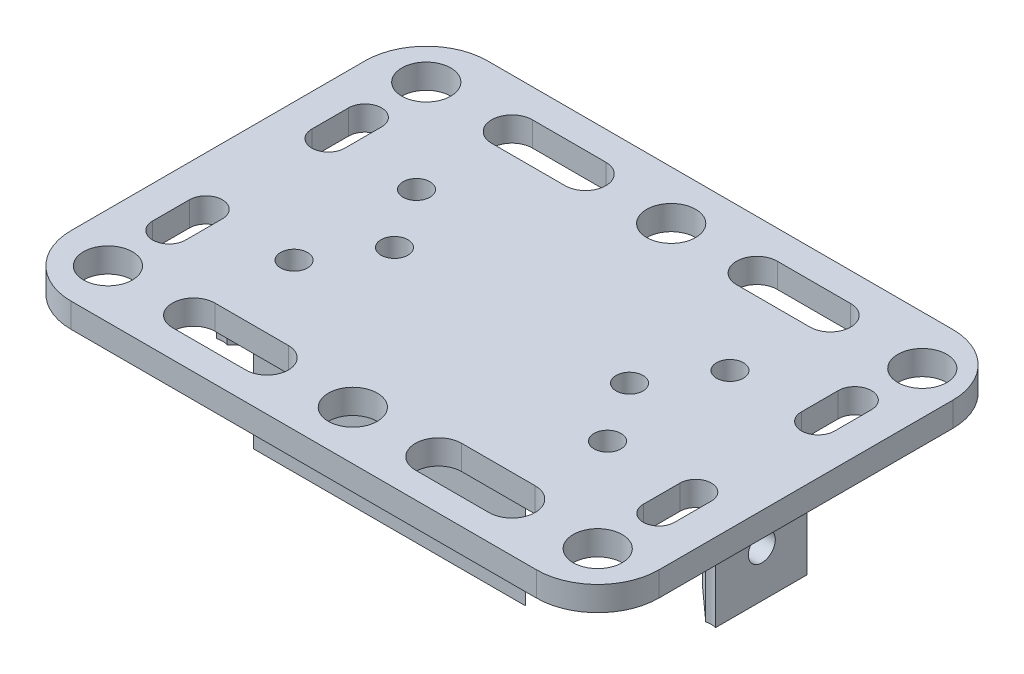
SolidWorks part; units mm, degrees
ref_plane "Front Plane" through (0, 0, 0) normal (0, 0, 1) x (1, 0, 0)
ref_plane "Top Plane" through (0, 0, 0) normal (0, 1, 0) x (1, 0, 0)
ref_plane "Right Plane" through (0, 0, 0) normal (1, 0, 0) x (0, 0, -1)
sketch "Sketch2" plane through (0, 0, 0) normal (0, 1, 0) x (1, 0, 0)
  line L0 (0, -55) -> (0, 55) construction
  line L1 (0, -42.5) -> (60, -42.5)
  line L2 (0, -42.5) -> (0, 42.5)
  line L3 (0, 42.5) -> (60, 42.5)
  line L4 (60, -42.5) -> (60, 42.5)
  line L5 (-55, 0) -> (55, 0) construction
  dimension "D1" = 60
  dimension "D2" = 85
  dimension "D3" = 42.5
extrude "Boss-Extrude1" add sketch "Sketch2" along normal blind 5
sketch "Sketch3" plane through (0, 0, 0) normal (0, -1, 0) x (1, 0, 0)
  line L0 (0, 25) -> (0, -25)
  line L1 (0, -2.75) -> (0, 2.75) construction
  line L2 (0, 25) -> (27.7753, 25)
  line L3 (27.7753, -25) -> (0.01, 0)
  line L4 (0.01, 0) -> (27.7753, 25)
  line L5 (2.75, 0) -> (-2.75, 0) construction
  line L6 (0, -25) -> (27.7753, -25)
  line L7 (0.01, 0) -> (38.51, 0) construction
  line L8 (38.51, 0) -> (51.01, 11.2551)
  line L10 (51.01, -11.2551) -> (38.51, 0)
  line L11 (51.01, 11.2551) -> (51.01, -11.2551)
  dimension "D1" = 42
  dimension "D2" = 42
  dimension "D3" = 0.01
  dimension "D4" = 38.5
  dimension "D5" = 12.5
  dimension "D6" = 25
  dimension "D7" = 42
  dimension "D8" = 25
  dimension "D9" = 42
extrude "Boss-Extrude2" add sketch "Sketch3" along normal blind 20
extrude "Boss-Extrude3" add sketch "Sketch3<2>" along normal blind 20
sketch "Sketch3<2>" plane through (0, 0, 0) normal (0, -1, 0) x (1, 0, 0) same geometry as "Sketch3"
fillet "Fillet1" radius 10 1 edges at (0.01, -10, 0)
fillet "Fillet2" radius 5 1 edges at (38.51, -10, 0)
fillet "Fillet3" radius 12.5 2 edges at (60, 2.5, 42.5) (60, 2.5, -42.5)
mirror "Mirror1" about plane through (0, 0, 0) normal (1, 0, 0) of "Fillet3", "Fillet2", "Fillet1", "Boss-Extrude3", "Boss-Extrude2", "Boss-Extrude1"
sketch "Sketch4" plane through (0, 5, 0) normal (0, 1, 0) x (1, 0, 0)
  line L1 (0, -2.75) -> (0, 2.75) construction
  line L4 (-47.5, -42.5) -> (47.5, -42.5) construction
  line L5 (47.5, 42.5) -> (-47.5, 42.5) construction
  line L6 (-32.5, 32.5) -> (-17.5, 32.5) construction
  line L7 (-32.5, 36.6576) -> (-17.5, 36.6576)
  line L8 (-32.5, 28.3424) -> (-17.5, 28.3424)
  line L9 (17.5, 32.5) -> (32.5, 32.5) construction
  line L10 (17.5, 36.6576) -> (32.5, 36.6576)
  line L11 (17.5, 28.3424) -> (32.5, 28.3424)
  line L12 (17.5, -32.5) -> (32.5, -32.5) construction
  line L13 (17.5, -27.7668) -> (32.5, -27.7668)
  line L14 (17.5, -37.2332) -> (32.5, -37.2332)
  line L15 (-32.5, -32.5) -> (-17.5, -32.5) construction
  line L16 (-32.5, -28.156) -> (-17.5, -28.156)
  line L17 (-32.5, -36.844) -> (-17.5, -36.844)
  line L18 (50, -20) -> (50, -12.5) construction
  line L19 (46.8051, -20) -> (46.8051, -12.5)
  line L20 (53.1949, -20) -> (53.1949, -12.5)
  line L21 (50, 20) -> (50, 12.5) construction
  line L22 (53.3895, 20) -> (53.3895, 12.5)
  line L23 (46.6105, 20) -> (46.6105, 12.5)
  line L24 (-50, 20) -> (-50, 12.5) construction
  line L25 (-46.6279, 20) -> (-46.6279, 12.5)
  line L26 (-53.3721, 20) -> (-53.3721, 12.5)
  line L27 (-50, -12.5) -> (-50, -20) construction
  line L28 (-46.6279, -12.5) -> (-46.6279, -20)
  line L29 (-53.3721, -12.5) -> (-53.3721, -20)
  circle A0 centre (-50, 32.5) radius 5
  circle A1 centre (0, 32.5) radius 5
  circle A2 centre (51.2765, 32.5) radius 5
  circle A3 centre (50, -32.5) radius 5
  circle A4 centre (0, -32.5) radius 5
  circle A5 centre (-50, -32.5) radius 5
  arc A8 (-32.5, 36.6576) -> (-32.5, 28.3424) centre (-32.5, 32.5) ccw
  arc A9 (-17.5, 28.3424) -> (-17.5, 36.6576) centre (-17.5, 32.5) ccw
  arc A10 (17.5, 36.6576) -> (17.5, 28.3424) centre (17.5, 32.5) ccw
  arc A11 (32.5, 28.3424) -> (32.5, 36.6576) centre (32.5, 32.5) ccw
  arc A12 (17.5, -27.7668) -> (17.5, -37.2332) centre (17.5, -32.5) ccw
  arc A13 (32.5, -37.2332) -> (32.5, -27.7668) centre (32.5, -32.5) ccw
  arc A14 (-32.5, -28.156) -> (-32.5, -36.844) centre (-32.5, -32.5) ccw
  arc A15 (-17.5, -36.844) -> (-17.5, -28.156) centre (-17.5, -32.5) ccw
  arc A16 (46.8051, -20) -> (53.1949, -20) centre (50, -20) ccw
  arc A17 (53.1949, -12.5) -> (46.8051, -12.5) centre (50, -12.5) ccw
  arc A18 (53.3895, 20) -> (46.6105, 20) centre (50, 20) ccw
  arc A19 (46.6105, 12.5) -> (53.3895, 12.5) centre (50, 12.5) ccw
  arc A20 (-46.6279, 20) -> (-53.3721, 20) centre (-50, 20) ccw
  arc A21 (-53.3721, 12.5) -> (-46.6279, 12.5) centre (-50, 12.5) ccw
  arc A22 (-46.6279, -12.5) -> (-53.3721, -12.5) centre (-50, -12.5) ccw
  arc A23 (-53.3721, -20) -> (-46.6279, -20) centre (-50, -20) ccw
  point P30 (-25, 32.5)
  point P35 (25, 32.5)
  point P42 (25, -32.5)
  point P49 (-25, -32.5)
  point P56 (50, -16.25)
  point P63 (50, 16.25)
  point P70 (-50, 16.25)
  point P77 (-50, -16.25)
  dimension "D2" = 10
  dimension "D3" = 10
  dimension "D4" = 10
  dimension "D6" = 10
  dimension "D7" = 10
  dimension "D8" = 10
  dimension "D11" = 10
  dimension "D12" = 10
  dimension "D13" = 15
  dimension "D14" = 15
  dimension "D15" = 15
  dimension "D16" = 15
  dimension "D17" = 7.5
  dimension "D18" = 7.5
  dimension "D19" = 7.5
  dimension "D20" = 7.5
  dimension "D26" = 50
  dimension "D27" = 25
  dimension "D28" = 25
  dimension "D29" = 25
  dimension "D30" = 25
extrude "Cut-Extrude1" cut sketch "Sketch4" against normal through all
sketch "Sketch5" plane through (51.01, 0, 0) normal (1, 0, 0) x (0, 0, -1)
  line L0 (0, 13.75) -> (0, -13.75) construction
  circle A0 centre (0, -10.5) radius 2.75
  dimension "D1" = 5.5
  dimension "D2" = 10.5
extrude "Cut-Extrude2" cut sketch "Sketch5" against normal through all
sketch "Sketch6" plane through (0, 0, 0) normal (0, -1, 0) x (1, 0, 0)
  line L0 (13.75, 0) -> (-13.75, 0) construction
  line L1 (0, -13.75) -> (0, 13.75) construction
  circle A0 centre (32, 12.5) radius 2.75
  circle A1 centre (24, 0) radius 2.75
  circle A2 centre (32, -12.5) radius 2.75
  circle A3 centre (-32, 12.5) radius 2.75
  circle A4 centre (-24, 0) radius 2.75
  circle A5 centre (-32, -12.5) radius 2.75
  dimension "D1" = 5.5
  dimension "D2" = 5.5
  dimension "D3" = 5.5
  dimension "D4" = 5.5
  dimension "D5" = 5.5
  dimension "D6" = 5.5
  dimension "D7" = 24
  dimension "D8" = 24
  dimension "D9" = 32
  dimension "D10" = 32
  dimension "D11" = 12.5
  dimension "D12" = 12.5
  dimension "D13" = 12.5
  dimension "D14" = 12.5
extrude "Cut-Extrude3" cut sketch "Sketch6" against normal blind 10
